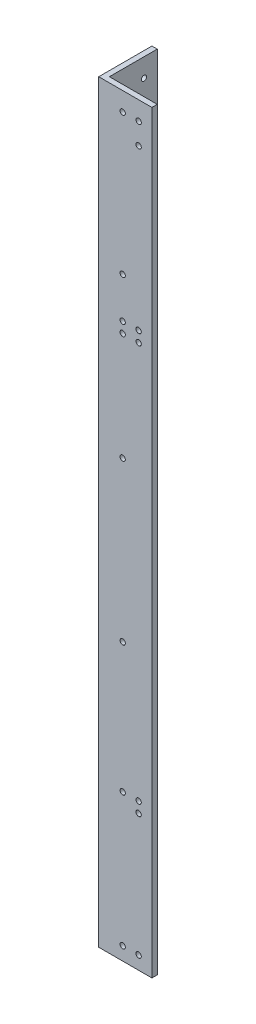
SolidWorks part; units mm, degrees
ref_plane "Front Plane" through (0, 0, 0) normal (0, 0, 1) x (1, 0, 0)
ref_plane "Top Plane" through (0, 0, 0) normal (0, 1, 0) x (1, 0, 0)
ref_plane "Right Plane" through (0, 0, 0) normal (1, 0, 0) x (0, 0, -1)
sketch "Sketch2" plane through (0, 0, 0) normal (0, 1, 0) x (1, 0, 0)
  line L0 (0, 31.75) -> (3.175, 31.75)
  line L1 (3.175, 31.75) -> (3.175, 3.175)
  line L2 (3.175, 3.175) -> (31.75, 3.175)
  line L3 (31.75, 3.175) -> (31.75, 0)
  line L4 (31.75, 0) -> (0, 0)
  line L5 (0, 0) -> (0, 31.75)
  point P9 (1.5875, 31.75)
  point P10 (31.75, 1.5875)
  dimension "D4" = 3.175
  dimension "D1" = 31.75
  dimension "D2" = 31.75
  dimension "D3" = 3.175
extrude "Boss-Extrude1" add sketch "Sketch2" along normal blind 450
sketch "BackSideHoles-Sketch3" plane through (0, 0, 0) normal (0, 0, 1) x (1, 0, 0)
  line L0 (0, 0) -> (31.75, 0) construction
  line L1 (0, 450) -> (0, 0) construction
  circle A1 centre (23.8125, 81.1125) radius 1.5875
  circle A2 centre (14.2875, 87.4625) radius 1.5875
  circle A3 centre (23.8125, 87.4625) radius 1.5875
  circle A4 centre (14.2875, 438.8875) radius 1.5875
  circle A6 centre (23.8125, 438.8875) radius 1.5875
  circle A7 centre (23.8125, 426.1875) radius 1.5875
  circle A10 centre (14.2875, 330.7776) radius 1.5875
  circle A11 centre (23.8125, 330.7776) radius 1.5875
  circle A12 centre (14.2875, 324.4276) radius 1.5875
  circle A13 centre (23.8125, 324.4276) radius 1.5875
  circle A14 centre (14.2875, 165) radius 1.5875
  circle A15 centre (14.2875, 260) radius 1.5875
  circle A17 centre (14.2875, 7.9375) radius 1.5875
  circle A18 centre (23.8125, 7.9375) radius 1.5875
  circle A19 centre (14.2875, 355) radius 1.5875
  dimension "D4" = 3.175
  dimension "D8" = 11.1125
  dimension "D7" = 6.35
  dimension "D10" = 330.7776
  dimension "D11" = 165
  dimension "D12" = 95
  dimension "D6" = 7.9375
  dimension "D5" = 6.35
  dimension "D14" = 81.1125
  dimension "D3" = 9.525
  dimension "D2" = 14.2875
  dimension "D9" = 12.7
  dimension "D13" = 95
sketch "RightSideHoles-Sketch4" plane through (0, 0, 0) normal (-1, 0, 0) x (0, 0, 1)
  line L0 (-31.75, 450) -> (0, 450) construction
  line L1 (0, 450) -> (0, 0) construction
  line L3 (-31.75, 0) -> (0, 0) construction
  circle A0 centre (-23.8125, 81.1125) radius 1.5875
  circle A2 centre (-23.8125, 87.4625) radius 1.5875
  circle A4 centre (-23.8125, 438.8875) radius 1.5875
  circle A5 centre (-14.2875, 426.1875) radius 1.5875
  circle A6 centre (-23.8125, 426.1875) radius 1.5875
  circle A10 centre (-23.8125, 332.3776) radius 1.5875
  circle A11 centre (-14.2875, 332.3776) radius 1.5875
  circle A12 centre (-23.8125, 297.4526) radius 1.5875
  circle A13 centre (-14.2875, 297.4526) radius 1.5875
  circle A14 centre (-23.8125, 7.9375) radius 1.5875
  circle A15 centre (-14.2875, 7.9375) radius 1.5875
  circle A16 centre (-14.2875, 165) radius 1.5875
  circle A17 centre (-14.2875, 260) radius 1.5875
  circle A19 centre (-14.2875, 81.1125) radius 1.5875
  circle A20 centre (-14.2875, 355) radius 1.5875
  dimension "D4" = 3.175
  dimension "D5" = 6.35
  dimension "D2" = 14.2875
  dimension "D13" = 95
  dimension "D6" = 11.1125
  dimension "D8" = 7.9375
  dimension "D9" = 34.925
  dimension "D7" = 12.7
  dimension "D10" = 332.3776
  dimension "D12" = 165
  dimension "D3" = 81.1125
  dimension "D11" = 9.525
  dimension "D14" = 95
extrude "BackSideHoles-Cut-Extrude1" cut sketch "BackSideHoles-Sketch3" against normal blind 3.175
extrude "RightSideHoles-Cut-Extrude2" cut sketch "RightSideHoles-Sketch4" against normal blind 3.175
equation "\"RailThickness\"= .125in'Spec"
equation "\"VSWidth\"= 1.25in'Spec"
equation "\"VSHeight\"= 1.25in'Spec"
equation "\"VSLength\"= 450mm"
equation "\"HoleOffsetFromEdge\"= \"RailThickness\" * 2.5"
equation "\"HoleOffsetFromSide\"= \"RailThickness\" * 3.5"
equation "\"LegHeight\"= 70mm'Space needed for PSU/Stepper/Electronics"
equation "\"VSBottomSideRailHoleY1FromBottomOfLowerRail\"= \"V1 BottomOfLowerRail\" + \"HoleOffsetFromSide\"'Equals 81.1125"
equation "\"VSSideRailHoleX1FromSide\"= \"HoleOffsetFromSide\" + \"RailThickness\""
equation "\"FasteningHoleDiameter\"= .125in"
equation "\"VSBottomSideRailHoleY2FromY1\"= \"LowerRailHeight\" - \"HoleOffsetFromSide\" - \"HoleOffsetFromEdge\"'Equals 6.35"
equation "\"VSTopSideRailHoleY1FromEdge\"= \"HoleOffsetFromEdge\" + \"RailThickness\""
equation "\"D4@BackSideHoles-Sketch3\" = \"FasteningHoleDiameter\""
equation "\"D1@Boss-Extrude1\"=\"VSLength\""
equation "\"D4@RightSideHoles-Sketch4\"=\"FasteningHoleDiameter\""
equation "\"D8@BackSideHoles-Sketch3\" = \"VSTopSideRailHoleY1FromEdge\""
equation "\"D6@RightSideHoles-Sketch4\"=\"VSTopSideRailHoleY1FromEdge\""
equation "\"VSMidSideRailHoleY1FromV8TopOfMidSideRail\"= \"V8 ToTopOfMidSideRail\" - \"HoleOffsetFromEdge\"'Equals 332.37764"
equation "\"LowerRailHeight\"= 1.00in"
equation "\"D2@Sketch2\"=\"VSWidth\""
equation "\"D1@Sketch2\"=\"VSHeight\""
equation "\"MidBackRailHeight\"= 1.00in"
equation "\"VSMidBackRailHoleY1FromV7TopOfMidBackRail\"= \"V7 ToTopOfMidBackRail\" - \"HoleOffsetFromEdge\"'Equals 330.77764"
equation "\"TopRailHeight\"= 1.25in"
equation "\"MidLeftOrRightSideRailHeight\"= 2.0in"
equation "\"D8@RightSideHoles-Sketch4\"=\"HoleOffsetFromEdge\""
equation "\"VSMidBackRailHoleY2FromY1\"= \"MidBackRailHeight\" - \"HoleOffsetFromSide\" - \"HoleOffsetFromEdge\"'Equals 6.35"
equation "\"VSMidSideRailHoleY2FromY1\"= \"MidLeftOrRightSideRailHeight\" - \"HoleOffsetFromEdge\" * 2'Equals 34.925"
equation "\"D7@BackSideHoles-Sketch3\"=\"VSMidBackRailHoleY2FromY1\""
equation "\"D9@RightSideHoles-Sketch4\"=\"VSMidSideRailHoleY2FromY1\""
equation "\"VSTopSideRailHoleY2FromY1\"= \"TopRailHeight\" - \"VSTopSideRailHoleY1FromEdge\" - \"HoleOffsetFromEdge\"'Equals 12.7"
equation "\"VSSideRailHoleX2FromX1\"= \"VSWidth\" - \"VSSideRailHoleX1FromSide\" - \"HoleOffsetFromEdge\""
equation "\"D7@RightSideHoles-Sketch4\"=\"VSTopSideRailHoleY2FromY1\""
equation "\"V1 BottomOfLowerRail\"= \"LegHeight\""
equation "\"StepperShaftLength\"= 24mm'Pulley will be attached to the end"
equation "\"ZAxisLeadScrewLength\"= 200mm"
equation "\"HotEndToTopOfXAxisGB\"= 63.315144mm'Measured from the100.Should be 63.315144"
equation "\"TopOfGBToBottomOfLinearRail\"= \"LinearGBWidth\" / 2 + \"LinearRailWidth\" / 2"
equation "\"LinearGBWidth\"= 27mm'Spec"
equation "\"V5 ToBottomOfXAxisLinearRail\"= \"V4 ToTopOfBuildPlate/HotEndTip\" + \"HotEndToTopOfXAxisGB\" - \"TopOfGBToBottomOfLinearRail\""
equation "\"LinearRailWidth\"= 12mm'Spec"
equation "\"V6 ToMiddleOfYAxisGantryBlock\"= \"V5 ToBottomOfXAxisLinearRail\" - \"GABHeight\" / 2'Equals 325.31514"
equation "\"GABUpperHeight\"= 6mm"
equation "\"GABMidWallHeight\"= 28mm'Must equal 28 or changes alignment"
equation "\"V7 ToBottomOfMidBackRail\"= \"V6 ToMiddleOfYAxisGantryBlock\" - \"StepperShaftLength\" / 2"
equation "\"D10@BackSideHoles-Sketch3\" = \"VSMidBackRailHoleY1FromV7TopOfMidBackRail\""
equation "\"D10@RightSideHoles-Sketch4\"=\"VSMidSideRailHoleY1FromV8TopOfMidSideRail\""
equation "\"BedToBuildPlateStandoffLength\"= 15mm"
equation "\"BuildPlateHeight\"= 8mm'Spec"
equation "\"V4 ToTopOfBuildPlate/HotEndTip\"= \"V2 ToBedAtTopOfZAxis\" + \"BedToBuildPlateStandoffLength\" + \"BuildPlateHeight\""
equation "\"V2 ToBedAtTopOfZAxis\"= \"V1 BottomOfLowerRail\" - \"LowerEnclosureThickness\" + \"StepperShaftLength\" + \"ZAxisLeadScrewLength\" - \"LM8UUHeight\" / 2"
equation "\"LM8UUHeight\"= 24mm'Spec"
equation "\"V8 ToTopOfMidSideRail\"= \"V6 ToMiddleOfYAxisGantryBlock\" + \"MidSideRailVerticalOffset\""
equation "\"VSEnclosureOffsets\"= ( \"VSLength\" - \"LegHeight\" ) / 4"
equation "\"D11@BackSideHoles-Sketch3\"=\"LegHeight\" + \"VSEnclosureOffsets\""
equation "\"D12@BackSideHoles-Sketch3\"=\"VSEnclosureOffsets\""
equation "\"D12@RightSideHoles-Sketch4\"=\"LegHeight\" + \"VSEnclosureOffsets\""
equation "\"D13@RightSideHoles-Sketch4\"=\"VSEnclosureOffsets\""
equation "\"D6@BackSideHoles-Sketch3\"=\"HoleOffsetFromEdge\""
equation "\"D5@BackSideHoles-Sketch3\"=\"VSBottomSideRailHoleY2FromY1\""
equation "\"D14@BackSideHoles-Sketch3\"=\"VSBottomSideRailHoleY1FromBottomOfLowerRail\""
equation "\"D2@BackSideHoles-Sketch3\"=\"VSSideRailHoleX1FromSide\""
equation "\"D9@BackSideHoles-Sketch3\"=\"VSTopSideRailHoleY2FromY1\""
equation "\"D3@RightSideHoles-Sketch4\"=\"VSBottomSideRailHoleY1FromBottomOfLowerRail\""
equation "\"D5@RightSideHoles-Sketch4\"=\"VSBottomSideRailHoleY2FromY1\""
equation "\"D2@RightSideHoles-Sketch4\"=\"VSSideRailHoleX1FromSide\""
equation "\"D11@RightSideHoles-Sketch4\"=\"VSSideRailHoleX2FromX1\""
equation "\"LowerEnclosureThickness\"= 5mm"
equation "\"V7 ToTopOfMidBackRail\"= \"V7 ToBottomOfMidBackRail\" + \"MidBackRailHeight\""
equation "\"GABLowerHeight\"= 3mm"
equation "\"GABHeight\"= \"GABLowerHeight\" + \"GABMidWallHeight\" + \"GABUpperHeight\""
equation "\"D13@BackSideHoles-Sketch3\"=\"VSEnclosureOffsets\""
equation "\"D14@RightSideHoles-Sketch4\"=\"VSEnclosureOffsets\""
equation "\"MidSideRailVerticalOffset\"= \"LinearRailWidth\" + 3mm'Allows space for RodStabilizer to attach to bottom of MidSideRail"
